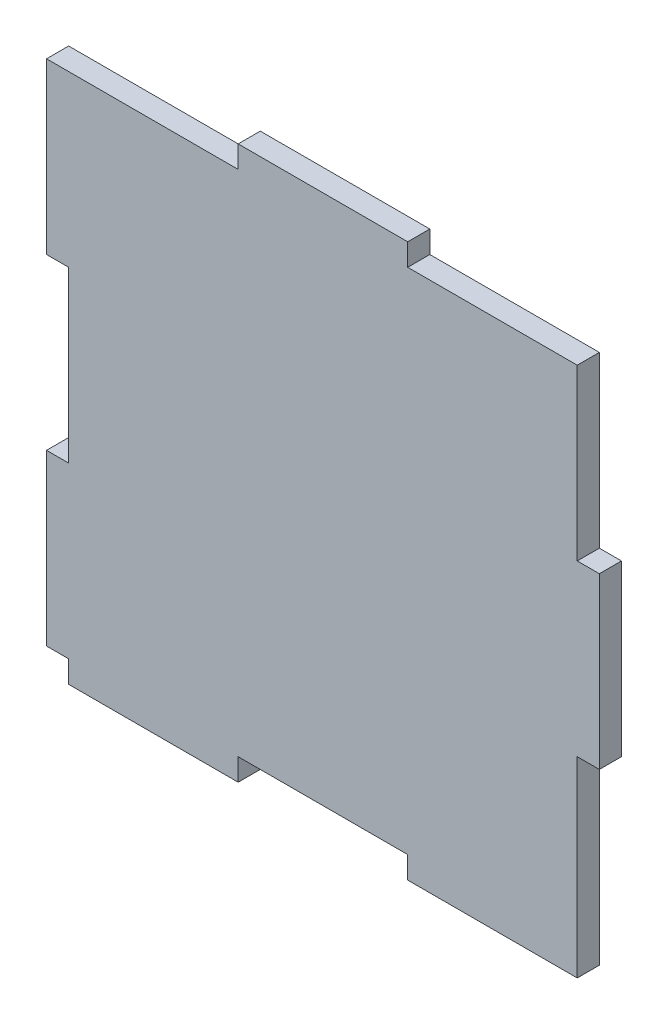
SolidWorks part; units mm, degrees
ref_plane "Front Plane" through (0, 0, 0) normal (0, 0, 1) x (1, 0, 0)
ref_plane "Top Plane" through (0, 0, 0) normal (0, 1, 0) x (1, 0, 0)
ref_plane "Right Plane" through (0, 0, 0) normal (1, 0, 0) x (0, 0, -1)
sketch "Sketch1" plane through (0, 0, 0) normal (0, 0, 1) x (1, 0, 0)
  line L0 (-69, 69) -> (-23, 69)
  line L5 (-75, -75) -> (75, -75) construction
  line L6 (-75, -75) -> (-75, 75) construction
  line L7 (-75, 75) -> (75, 75) construction
  line L8 (75, -75) -> (75, 75) construction
  line L9 (75, 23) -> (69, 23)
  line L10 (69, -23) -> (75, -23)
  line L11 (-69, -69) -> (69, -69) construction
  line L12 (-69, -69) -> (-69, 69) construction
  line L13 (-69, 69) -> (69, 69) construction
  line L14 (69, -69) -> (69, 69) construction
  line L15 (-69, -69) -> (69, 69) construction
  line L16 (69, -69) -> (69, -23)
  line L17 (-23, 69) -> (-23, 75)
  line L18 (-23, 75) -> (23, 75)
  line L19 (23, 75) -> (23, 69)
  line L20 (23, 69) -> (69, 69)
  line L21 (75, -23) -> (75, 23)
  line L22 (69, 23) -> (69, 69)
  line L23 (-75, 23) -> (-69, 23)
  line L24 (-69, 69) -> (-75, 69)
  line L25 (-75, 69) -> (-75, 23)
  line L26 (69, -69) -> (69, -75)
  line L27 (69, -75) -> (23, -75)
  line L28 (23, -75) -> (23, -69)
  line L29 (23, -69) -> (-23, -69)
  line L30 (-23, -69) -> (-23, -75)
  line L31 (-23, -75) -> (-69, -75)
  line L32 (-69, -75) -> (-69, -69)
  line L33 (-69, 23) -> (-69, -23)
  line L34 (-69, -23) -> (-75, -23)
  line L35 (-75, -23) -> (-75, -69)
  line L36 (-75, -69) -> (-69, -69)
  point P0 (0, 0)
  point P6 (-7, -7)
  point P11 (23, 75)
  point P19 (0, 0)
  point P26 (0, -75)
  point P27 (-75, 0)
  point P29 (23.0148, -69)
  dimension "D1" = 150
  dimension "D2" = 150
  dimension "D3" = 6
  dimension "D4" = 138
  dimension "D5" = 46
  dimension "D6" = 6
  dimension "D7" = 6
extrude "Boss-Extrude1" add sketch "Sketch1" along normal blind 6
